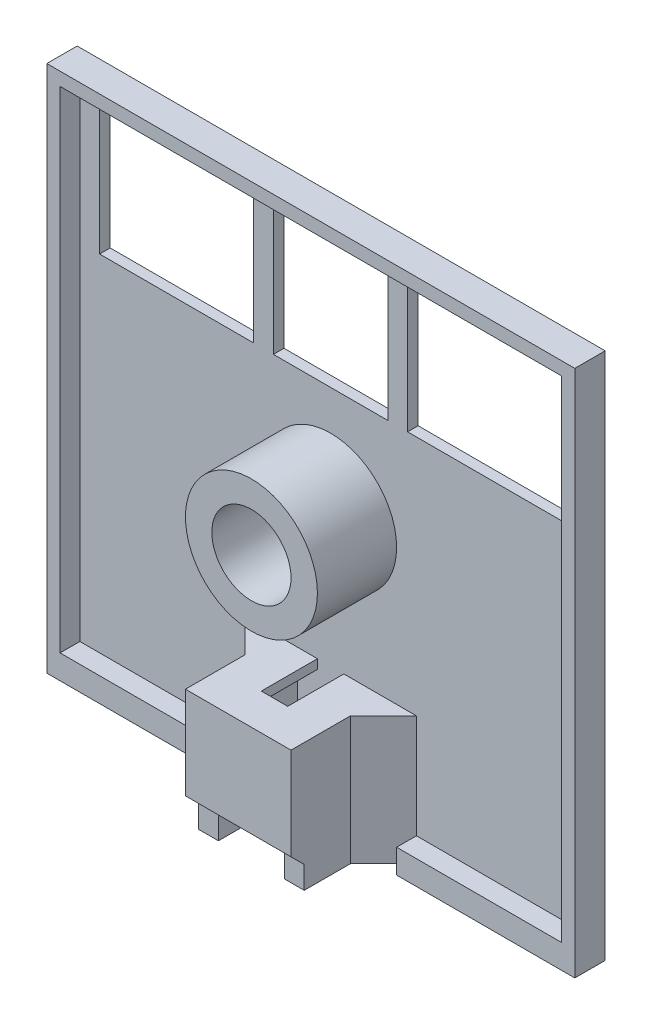
SolidWorks part; units mm, degrees
ref_plane "Front Plane" through (0, 0, 0) normal (0, 0, 1) x (1, 0, 0)
ref_plane "Top Plane" through (0, 0, 0) normal (0, 1, 0) x (1, 0, 0)
ref_plane "Right Plane" through (0, 0, 0) normal (1, 0, 0) x (0, 0, -1)
sketch "Sketch1" plane through (0, 0, 0) normal (0, 0, 1) x (1, 0, 0)
  line L1 (-40, -40) -> (40, -40)
  line L2 (-40, -40) -> (-40, 40)
  line L3 (-40, 40) -> (40, 40)
  line L4 (40, -40) -> (40, 40)
  line L5 (-40, -40) -> (40, 40) construction
  line L6 (-40, 40) -> (40, -40) construction
  point P0 (0, 0)
extrude "Boss-Extrude1" add sketch "Sketch1" along normal blind 1.6
sketch "Sketch2" plane through (0, 0, 1.6) normal (0, 0, 1) x (1, 0, 0)
  circle A0 centre (0, 0) radius 10
  circle A1 centre (0, 0) radius 6
  dimension "D1" = 20
extrude "Boss-Extrude2" add sketch "Sketch2" along normal blind 12
sketch "Sketch3" plane through (0, 0, 1.6) normal (0, 0, 1) x (1, 0, 0)
  line L0 (-40, 40) -> (-40, -40) construction
  line L1 (-35, 36) -> (-11.67, 36)
  line L2 (-35, 36) -> (-35, 16)
  line L3 (-35, 16) -> (-11.67, 16)
  line L4 (35, 36) -> (35, 16)
  line L5 (40, -40) -> (40, 40) construction
  line L6 (40, 40) -> (-40, 40) construction
  line L7 (-11.67, 36) -> (-11.67, 16)
  line L8 (11.66, 36) -> (11.66, 16)
  line L9 (-8.67, 36) -> (-8.67, 16)
  line L10 (8.66, 36) -> (8.66, 16)
  line L11 (-8.67, 36) -> (8.66, 36)
  line L12 (-8.67, 16) -> (8.66, 16)
  line L13 (11.66, 16) -> (35, 16)
  line L14 (11.66, 36) -> (35, 36)
  circle A0 centre (0, 0) radius 10 construction
  dimension "D1" = 5
  dimension "D2" = 5
  dimension "D3" = 4
  dimension "D4" = 16
  dimension "D5" = 20
  dimension "D6" = 3
  dimension "D7" = 2
  dimension "D8" = 2
extrude "Cut-Extrude1" cut sketch "Sketch3" against normal blind 12
sketch "Sketch4" plane through (0, 0, 1.6) normal (0, 0, 1) x (1, 0, 0)
  line L0 (-40, -40) -> (40, -40) construction
  line L2 (-5, -40) -> (-5, -25)
  line L4 (5, -40) -> (5, -25)
  line L5 (-8, -40) -> (-8, -22)
  line L6 (-8, -22) -> (-5, -22)
  line L8 (8, -40) -> (8, -22)
  line L11 (8, -40) -> (5, -40)
  line L13 (-5, -40) -> (-8, -40)
  line L14 (-8, -43) -> (8, -43) construction
  line L15 (-5, -40) -> (5, -40) construction
  line L16 (-8, -43) -> (-8, -22) construction
  line L17 (8, -43) -> (8, -22) construction
  line L18 (-5, -25) -> (-5, -22)
  line L20 (5, -22) -> (5, -25)
  line L21 (5, -22) -> (8, -22)
  line L22 (-5, -25) -> (5, -25) construction
  line L23 (-8, -22) -> (8, -22) construction
  point P0 (0, -40)
  dimension "D1" = 3
  dimension "D2" = 3
extrude "Boss-Extrude3" add sketch "Sketch4" along normal blind 12
sketch "Sketch5" plane through (0, 0, 1.6) normal (0, 0, 1) x (1, 0, 0)
  line L0 (0, -22) -> (0, -10) construction
  line L1 (-2, -20.6) -> (-2, -22)
  line L2 (-8, -22) -> (-2, -22)
  line L3 (-8, -22) -> (-8, -20.6)
  line L4 (-8, -20.6) -> (-2, -20.6)
  line L5 (8, -22) -> (8, -20.6)
  line L7 (2, -22) -> (2, -20.6)
  line L8 (2, -20.6) -> (8, -20.6)
  line L9 (2, -22) -> (8, -22)
  circle A0 centre (0, 0) radius 10 construction
  dimension "D1" = 12
  dimension "D2" = 4
  dimension "D3" = 6
  dimension "D4" = 1.4
extrude "Boss-Extrude4" add sketch "Sketch5" along normal blind 12
sketch "Sketch6" plane through (0, 0, 13.6) normal (0, 0, 1) x (1, 0, 0)
  line L0 (8, -40) -> (8, -20.6) construction
  line L1 (-8, -20.6) -> (8, -20.6)
  line L2 (-8, -20.6) -> (-8, -34.6)
  line L3 (-8, -34.6) -> (8, -34.6)
  line L4 (8, -20.6) -> (8, -34.6)
extrude "Boss-Extrude5" add sketch "Sketch6" along normal blind 2
chamfer "Chamfer1" distance 2 angle 45 2 edges at (6.5, -34.6, 13.6) (-6.5, -34.6, 13.6)
sketch "Sketch7" plane through (0, 0, 13.6) normal (0, 0, -1) x (-1, 0, 0)
  line L1 (2, -20.6) -> (-2, -20.6)
  line L2 (2, -20.6) -> (2, -22)
  line L3 (2, -22) -> (-2, -22)
  line L4 (-2, -20.6) -> (-2, -22)
extrude "Boss-Extrude6" add sketch "Sketch7" along normal blind 3.5
chamfer "Chamfer2" distance 5 angle 45 2 edges at (-8, -30.3, 1.6) (8, -30.3, 1.6)
sketch "Sketch8" plane through (0, 0, 1.6) normal (0, 0, 1) x (1, 0, 0)
  line L0 (-13, -36.3398) -> (-13, -40)
  line L1 (-40, 40) -> (40, 40)
  line L2 (-40, 40) -> (-40, -40)
  line L3 (-40, -40) -> (-13, -40)
  line L4 (40, 40) -> (40, -40)
  line L5 (-38, 38) -> (38, 38)
  line L6 (-38, 38) -> (-38, -36.3398)
  line L7 (-38, -36.3398) -> (-13, -36.3398)
  line L8 (38, 38) -> (38, -36.3398)
  line L9 (-13, -40) -> (-13, -20.6) construction
  line L10 (13, -36.3398) -> (13, -40)
  line L11 (13, -20.6) -> (13, -40) construction
  line L13 (13, -36.3398) -> (38, -36.3398)
  line L14 (13, -40) -> (40, -40)
  dimension "D1" = 2
  dimension "D2" = 2
  dimension "D3" = 2
extrude "Boss-Extrude7" add sketch "Sketch8" along normal blind 3
